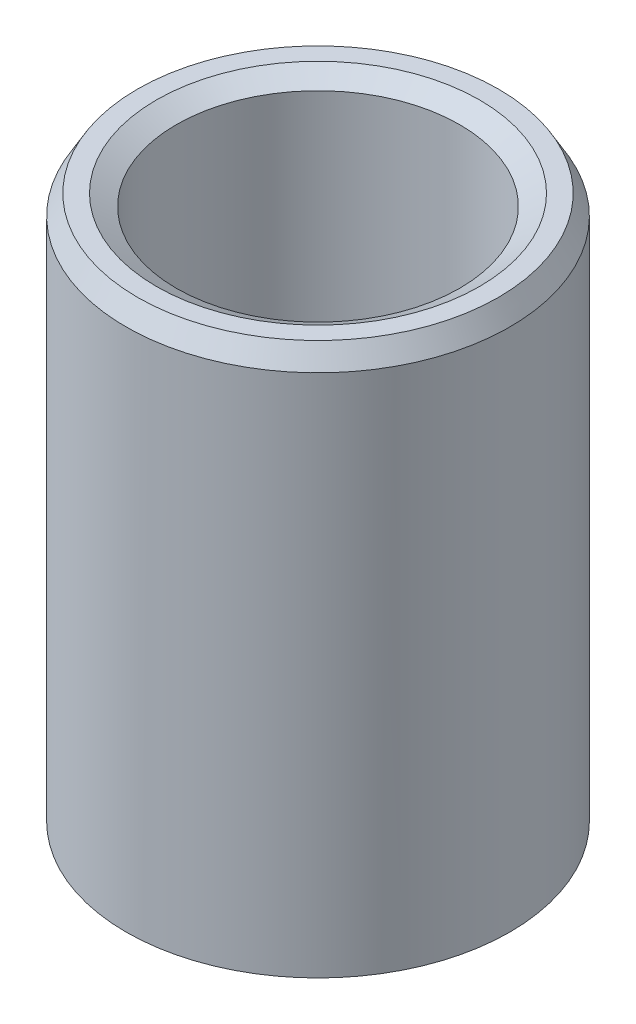
SolidWorks part; units mm, degrees
ref_plane "Front Plane" through (0, 0, 0) normal (0, 0, 1) x (1, 0, 0)
ref_plane "Top Plane" through (0, 0, 0) normal (0, 1, 0) x (1, 0, 0)
ref_plane "Right Plane" through (0, 0, 0) normal (1, 0, 0) x (0, 0, -1)
sketch "Sketch1" plane through (0, 0, 0) normal (0, 1, 0) x (1, 0, 0)
  circle A0 centre (0, 0) radius 27.5
  dimension "SLEEVE_OD" = 55
extrude "Boss-Extrude1" add sketch "Sketch1" along normal blind 79.59
sketch "Sketch2" plane through (0, 0, 0) normal (0, 1, 0) x (1, 0, 0)
  circle A0 centre (0, 0) radius 20.3104
  dimension "BORE_D" = 40.6207
extrude "Cut-Extrude1" cut sketch "Sketch2" along normal through all
chamfer "Chamfer1" distance 2.8449 angle 30 4 edges at (0, 79.59, 20.3104) (0, 0, 20.3104) (0, 0, 27.5) (0, 79.59, 27.5) first distance on face at (0, 79.59, 20.3104) first distance on face at (0, 0, 20.3104) first distance on face at (0, 79.59, 27.5)
